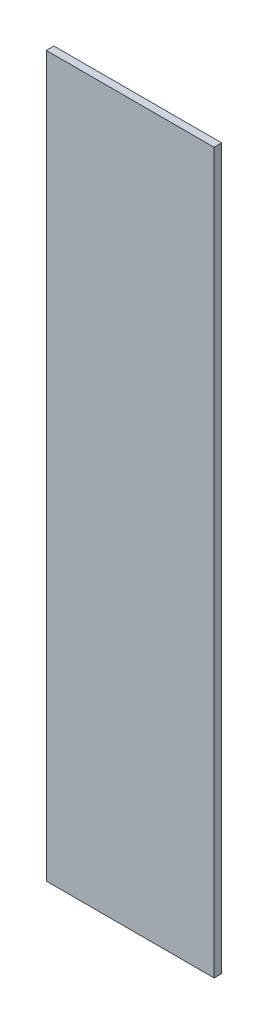
SolidWorks part; units mm, degrees
ref_plane "Front Plane" through (0, 0, 0) normal (0, 0, 1) x (1, 0, 0)
ref_plane "Top Plane" through (0, 0, 0) normal (0, 1, 0) x (1, 0, 0)
ref_plane "Right Plane" through (0, 0, 0) normal (1, 0, 0) x (0, 0, -1)
sketch "Sketch1" plane through (0, 0, 0) normal (0, 0, 1) x (1, 0, 0)
  line L1 (830.4931, 1332.0449) -> (1390.4931, 1332.0449)
  line L2 (830.4931, 1332.0449) -> (830.4931, -1067.9551)
  line L3 (830.4931, -1067.9551) -> (1390.4931, -1067.9551)
  line L4 (1390.4931, 1332.0449) -> (1390.4931, -1067.9551)
  line L5 (830.4931, 1332.0449) -> (1390.4931, -1067.9551) construction
  line L6 (830.4931, -1067.9551) -> (1390.4931, 1332.0449) construction
  point P1 (1110.4931, 132.0449)
  point P6 (0, 0)
  point P7 (0, 0)
  point P8 (-75.1784, 0)
  point P9 (1025.013, 11.1936)
  point P10 (1390.4931, 1332.0449)
  dimension "D1" = 560
  dimension "D2" = 2400
extrude "Boss-Extrude1" add sketch "Sketch1" along normal blind 12.7 and the other way blind 12.7
